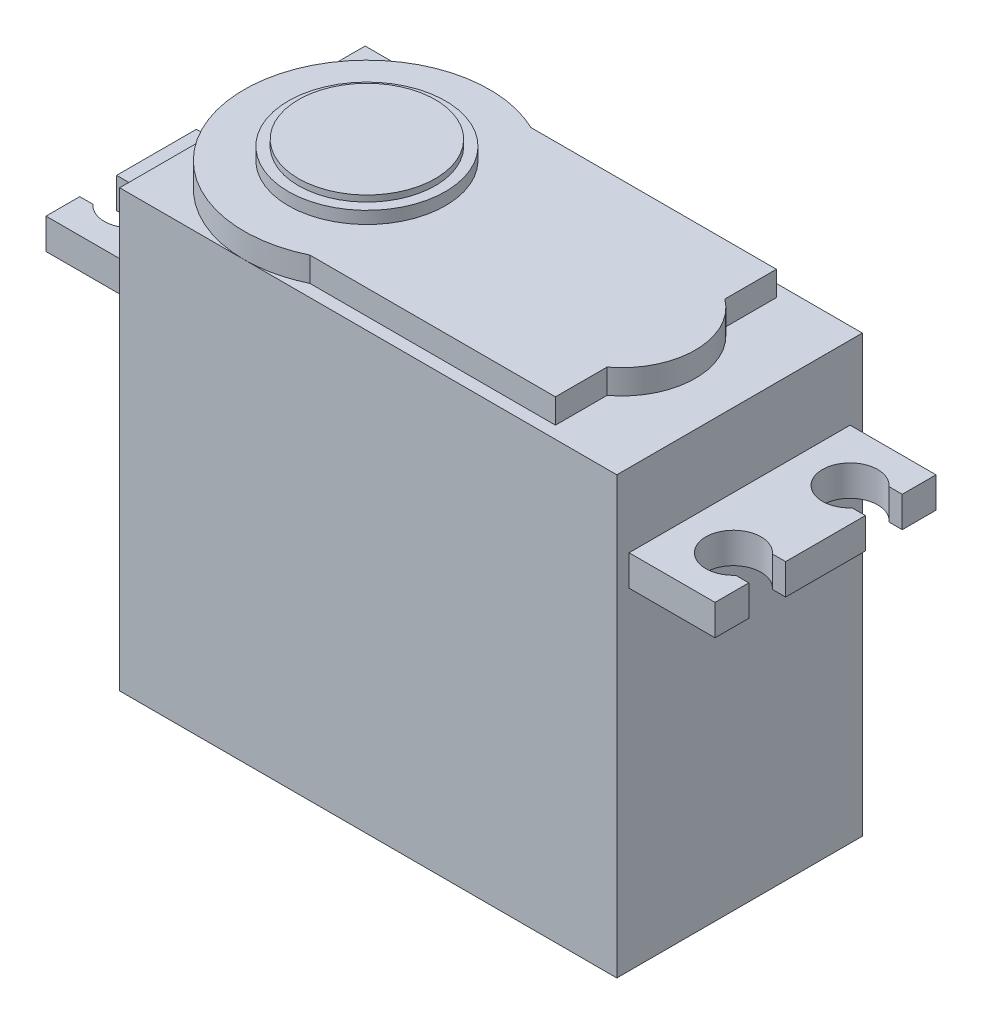
SolidWorks part; units mm, degrees
ref_plane "Front" through (0, 0, 0) normal (0, 0, 1) x (1, 0, 0)
ref_plane "Top" through (0, 0, 0) normal (0, 1, 0) x (1, 0, 0)
ref_plane "Right" through (0, 0, 0) normal (1, 0, 0) x (0, 0, -1)
sketch "Sketch1" plane through (0, 0, 0) normal (0, 1, 0) x (1, 0, 0)
  line L0 (-20.25, 10) -> (20.25, -10) construction
  line L1 (-20.25, -10) -> (20.25, -10)
  line L2 (-20.25, -10) -> (-20.25, 10)
  line L3 (-20.25, 10) -> (20.25, 10)
  line L4 (20.25, -10) -> (20.25, 10)
  line L5 (20.25, 10) -> (-20.25, -10) construction
  dimension "D1" = 20
  dimension "D2" = 40.5
extrude "Boss-Extrude1" add sketch "Sketch1" along normal blind 35.5
sketch "Sketch2" plane through (0, 35.5, 0) normal (0, 1, 0) x (1, 0, 0)
  line L0 (-5.75, -9) -> (14.25, -9)
  line L1 (14.25, -9) -> (14.25, -4.8)
  line L2 (-5.75, 9) -> (14.25, 9)
  line L3 (14.25, 9) -> (14.25, 4.8)
  line L4 (20.25, 10) -> (-20.25, 10) construction
  line L5 (-20.25, -10) -> (20.25, -10) construction
  line L6 (20.25, -10) -> (20.25, 10) construction
  line L7 (20.25, -10) -> (20.25, 10) construction
  arc A0 (-5.75, 9) -> (-5.75, -9) centre (-10.1089, 0) ccw
  arc A1 (14.25, 4.8) -> (14.25, -4.8) centre (10.65, 0) cw
  point P6 (0, 10)
  point P12 (16.65, 0)
  point P13 (20.25, 0)
  dimension "D1" = 1
  dimension "D3" = 4.2
  dimension "D2" = 1
  dimension "D4" = 3.6
  dimension "D5" = 20
  dimension "D6" = 6
extrude "Boss-Extrude2" add sketch "Sketch2" along normal blind 2
sketch "Sketch3" plane through (0, 37.5, 0) normal (0, 1, 0) x (1, 0, 0)
  circle A0 centre (-10.1089, 0) radius 6.4
  arc A1 (-10.1089, 10) -> (-10.1089, -10) centre (-10.1089, 0) ccw construction
  dimension "D1" = 12.8
extrude "Boss-Extrude3" add sketch "Sketch3" along normal blind 1
sketch "Sketch4" plane through (0, 38.5, 0) normal (0, 1, 0) x (1, 0, 0)
  circle A0 centre (-10.1089, 0) radius 5.575
  circle A1 centre (-10.1089, 0) radius 6.4 construction
  dimension "D1" = 11.15
extrude "Boss-Extrude4" add sketch "Sketch4" along normal blind 0.5
ref_plane "Plane1" through (0, 29.5, 0) normal (0, 1, 0) x (1, 0, 0)
sketch "Sketch5" plane through (0, 29.5, 0) normal (0, 1, 0) x (1, 0, 0)
  line L0 (20.25, 9) -> (27.25, 9)
  line L1 (20.25, -10) -> (20.25, 10) construction
  line L2 (27.25, 0) -> (27.25, 3.25)
  line L3 (20.25, 0) -> (27.25, 0)
  line L4 (20.25, 0) -> (20.25, 9)
  line L5 (20.25, 10) -> (-10.1089, 10) construction
  line L7 (24.5, 7) -> (24.5, 9) construction
  line L8 (27.25, 6.25) -> (27.25, 9)
  line L9 (26.1771, 6.25) -> (27.25, 6.25)
  line L10 (26.1771, 3.25) -> (27.25, 3.25)
  arc A0 (26.1771, 6.25) -> (26.1771, 3.25) centre (24.5, 4.75) ccw
  point P8 (0, 0)
  point P9 (22.25, 4.75)
  dimension "D4" = 4.5
  dimension "D5" = 2
  dimension "D1" = 1
  dimension "D2" = 9
  dimension "D3" = 7
  dimension "D6" = 3
  dimension "D7" = 2
extrude "Boss-Extrude5" add sketch "Sketch5" against normal blind 2.5
mirror "Mirror1" about plane through (0, 0, 0) normal (1, 0, 0) of "Boss-Extrude5"
mirror "Mirror2" about plane through (0, 0, 0) normal (0, 0, 1) of "Boss-Extrude5", "Mirror1"
